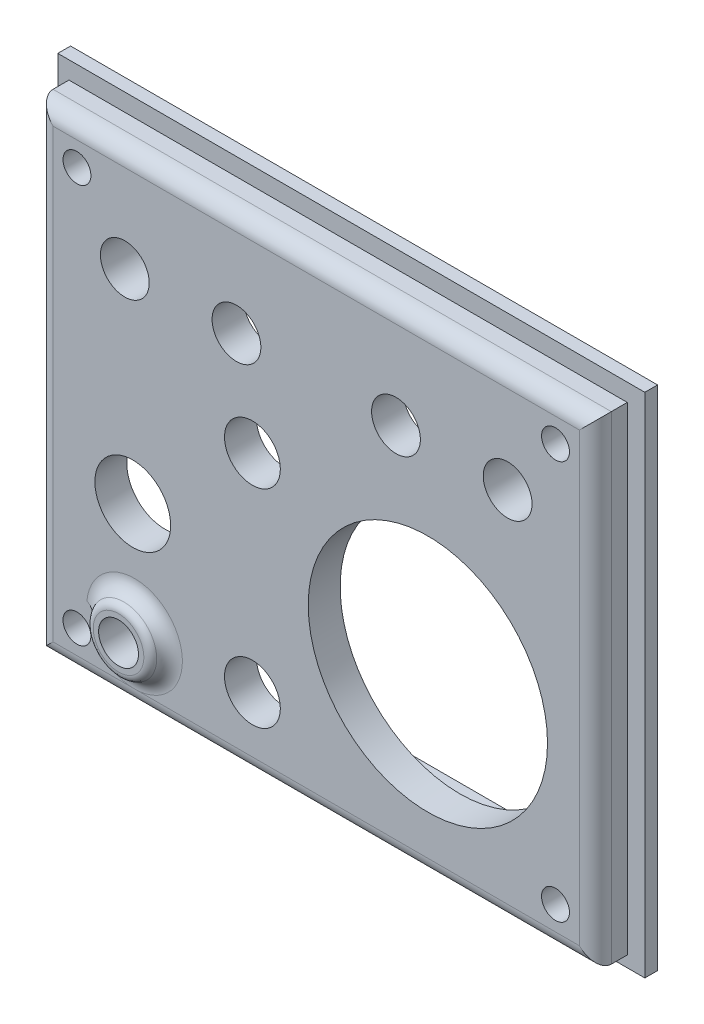
SolidWorks part; units mm, degrees
ref_plane "Спереди" through (0, 0, 0) normal (0, 0, 1) x (1, 0, 0)
ref_plane "Сверху" through (0, 0, 0) normal (0, 1, 0) x (1, 0, 0)
ref_plane "Справа" through (0, 0, 0) normal (1, 0, 0) x (0, 0, -1)
sketch "Sketch1" plane through (0, 0, 0) normal (0, 0, 1) x (1, 0, 0)
  line L1 (35, -30) -> (-35, -30)
  line L2 (35, -30) -> (35, 30)
  line L3 (35, 30) -> (-35, 30)
  line L4 (-35, -30) -> (-35, 30)
  line L5 (35, -30) -> (-35, 30) construction
  line L6 (35, 30) -> (-35, -30) construction
  point P0 (0, 0)
  dimension "D1" = 70
  dimension "D2" = 60
extrude "Boss-Extrude1" add sketch "Sketch1" along normal blind 4
sketch "Sketch2" plane through (0, 0, 0) normal (0, 0, -1) x (-1, 0, 0)
  line L0 (35, -30) -> (-35, -30) construction
  line L1 (-31.8, 26.8) -> (31.8, 26.8)
  line L2 (-31.8, 26.8) -> (-31.8, -26.8)
  line L3 (-31.8, -26.8) -> (31.8, -26.8)
  line L4 (31.8, 26.8) -> (31.8, -26.8)
  line L5 (-31.8, 26.8) -> (31.8, -26.8) construction
  line L6 (-31.8, -26.8) -> (31.8, 26.8) construction
  line L7 (-35, -30) -> (-35, 30) construction
  line L9 (28.8, -23.8) -> (-28.8, -23.8)
  line L10 (28.8, -23.8) -> (28.8, 23.8)
  line L11 (28.8, 23.8) -> (-28.8, 23.8)
  line L12 (-28.8, -23.8) -> (-28.8, 23.8)
  line L13 (28.8, -23.8) -> (-28.8, 23.8) construction
  line L14 (28.8, 23.8) -> (-28.8, -23.8) construction
  point P0 (0, 0)
  point P10 (0, 0)
  dimension "D1" = 3.2
  dimension "D2" = 3.2
  dimension "D3" = 3
  dimension "D4" = 3
extrude "Boss-Extrude2" add sketch "Sketch2" along normal blind 2
chamfer "Chamfer1" distance 0.5 angle 70 4 edges at (-31.8, 0, -2) (0, 26.8, -2) (31.8, 0, -2) (0, -26.8, -2) first distance on face at (0, 0, -2)
fillet "Fillet1" radius 2 4 edges at (0, 30, 4) (35, 0, 4) (0, -30, 4) (-35, 0, 4)
sketch "Sketch3" plane through (0, 0, 4) normal (0, 0, 1) x (1, 0, 0)
  line L0 (0, -41.7208) -> (0, 41.7208) construction
  line L1 (33, 17) -> (-33, 17) construction
  line L2 (-33, 28) -> (-33, -28) construction
  circle A1 centre (-24, 17) radius 3.0603
  circle A2 centre (10, 17) radius 3.0603
  circle A4 centre (-10, 17) radius 3.0603
  circle A5 centre (24, 17) radius 3.0603
  point P4 (0, 0)
  point P11 (0, 17)
  point P13 (-10, 17)
  dimension "D1" = 14
  dimension "D2" = 17
  dimension "D3" = 20
  dimension "D4" = 10
  dimension "D7" = 14
extrude "Cut-Extrude1" cut sketch "Sketch3" against normal through all
sketch "Sketch4" plane through (0, 0, 4) normal (0, 0, 1) x (1, 0, 0)
  line L0 (0, -40.1993) -> (0, 40.1993) construction
  line L1 (0, 0) -> (33, 0) construction
  line L2 (33, -28) -> (33, 28) construction
  line L3 (14, -8) -> (0, -8) construction
  circle A0 centre (14, -8) radius 15
  point P3 (0, 0)
  dimension "D1" = 30
  dimension "D2" = 8
  dimension "D3" = 14
extrude "Cut-Extrude2" cut sketch "Sketch4" against normal through all
sketch "Sketch5" plane through (0, 0, 4) normal (0, 0, 1) x (1, 0, 0)
  line L0 (-8, 28) -> (-8, -28) construction
  line L1 (33, 28) -> (-33, 28) construction
  line L2 (-33, -28) -> (33, -28) construction
  line L3 (14, -8) -> (-8, -8) construction
  line L4 (14, -8) -> (14, 28) construction
  circle A0 centre (-8, 5) radius 3.5
  circle A1 centre (-8, -21) radius 3.5
  dimension "D1" = 26
  dimension "D2" = 7
  dimension "D3" = 13
  dimension "D4" = 22
extrude "Cut-Extrude3" cut sketch "Sketch5" against normal through all
sketch "Sketch6" plane through (0, 0, 0) normal (0, 0, -1) x (-1, 0, 0)
  circle A0 centre (24, 17) radius 5
  circle A1 centre (-24, 17) radius 5
  circle A2 centre (-24, 17) radius 3.0603
  circle A3 centre (24, 17) radius 3.0603
  dimension "D1" = 10
extrude "Boss-Extrude3" add sketch "Sketch6" along normal blind 2
fillet "Fillet2" radius 1 3 edges at (28.8, 23.8, -1) (28.8, 18.4, -1) (28.8, 15.6, -1)
sketch "Sketch7" plane through (0, 0, -2) normal (0, 0, -1) x (-1, 0, 0)
  line L0 (15, 27.7408) -> (15, -32.2592)
  line L2 (15, -32.2592) -> (35, -32.2592)
  line L3 (35, -32.2592) -> (35, 27.7408)
  line L4 (35, 27.7408) -> (15, 27.7408)
  line L5 (35, 30) -> (35, -30) construction
  dimension "D1" = 20
  dimension "D2" = 60
extrude "Cut-Extrude4" cut sketch "Sketch7" against normal up to surface (2 mm away) up to face at (0, 0, 0)
sketch "Sketch8" plane through (0, 0, 0) normal (0, 0, -1) x (-1, 0, 0)
  line L0 (23, 30) -> (23, -30) construction
  line L1 (-35, 30) -> (35, 30) construction
  line L2 (35, -30) -> (-35, -30) construction
  line L3 (35, 30) -> (35, -30) construction
  line L4 (-14, -8) -> (23, -8) construction
  circle A0 centre (23, -8) radius 4.75
  dimension "D1" = 9.5
  dimension "D2" = 12
extrude "Cut-Extrude5" cut sketch "Sketch8" against normal through all
sketch "Sketch9" plane through (0, 0, 0) normal (0, 0, -1) x (-1, 0, 0)
  line L0 (35, 30) -> (35, -30) construction
  line L1 (-30, -25) -> (30, -25) construction
  line L2 (-30, -25) -> (-30, 25) construction
  line L3 (-30, 25) -> (30, 25) construction
  line L4 (30, -25) -> (30, 25) construction
  line L5 (-30, -25) -> (30, 25) construction
  line L6 (-30, 25) -> (30, -25) construction
  line L7 (35, -30) -> (-35, -30) construction
  circle A0 centre (30, 25) radius 1.75
  circle A1 centre (30, -25) radius 1.75
  circle A2 centre (-30, -25) radius 1.75
  circle A3 centre (-30, 25) radius 1.75
  point P0 (0, 0)
  dimension "D3" = 3.5
  dimension "D1" = 5
  dimension "D2" = 5
extrude "Cut-Extrude6" cut sketch "Sketch9" against normal through all both and the other way through all
sketch "Sketch10" plane through (0, 0, 0) normal (0, 0, -1) x (-1, 0, 0)
  line L0 (23, -8) -> (23, 1) construction
  circle A0 centre (23, 1) radius 2
  dimension "D2" = 4
  dimension "D1" = 9
extrude "Cut-Extrude7" cut sketch "Sketch10" against normal blind 2
sketch "Sketch11" plane through (0, 0, 0) normal (0, 0, -1) x (-1, 0, 0)
  circle A0 centre (24, 17) radius 5
  circle A1 centre (24, 17) radius 3.0603
  arc A2 (-27.1667, 13.1306) -> (-27.1667, 20.8694) centre (-24, 17) ccw construction
  circle A3 centre (-24, 17) radius 3.0603 construction
extrude "Boss-Extrude4" add sketch "Sketch11" along normal up to surface (2 mm away) up to face at (1.8381, -24.7536, -2)
sketch "Sketch12" plane through (0, 0, 0) normal (0, 0, -1) x (-1, 0, 0)
  circle A0 centre (-30, 25) radius 5
  circle A1 centre (-30, -25) radius 5
  dimension "D1" = 10
extrude "Cut-Extrude9" cut sketch "Sketch12" along normal through all
sketch "Sketch13" plane through (0, 0, 0) normal (0, 0, -1) x (-1, 0, 0)
  line L0 (35, -22) -> (-35, -22) construction
  line L1 (35, 30) -> (35, -30) construction
  line L2 (-35, -30) -> (-35, 30) construction
  line L3 (35, -30) -> (-35, -30) construction
  circle A0 centre (22.7832, -22) radius 2.5
  dimension "D1" = 5
  dimension "D2" = 8
extrude "Cut-Extrude10" cut sketch "Sketch13" against normal through all
sketch "Sketch14" plane through (0, 0, 0) normal (0, 0, -1) x (-1, 0, 0)
  line L1 (19.5332, -18.75) -> (26.0332, -18.75)
  line L2 (19.5332, -18.75) -> (19.5332, -25.25)
  line L3 (19.5332, -25.25) -> (26.0332, -25.25)
  line L4 (26.0332, -18.75) -> (26.0332, -25.25)
  line L5 (19.5332, -18.75) -> (26.0332, -25.25) construction
  line L6 (19.5332, -25.25) -> (26.0332, -18.75) construction
  line L7 (18.2832, -17.5) -> (27.2832, -17.5)
  line L8 (18.2832, -17.5) -> (18.2832, -26.5)
  line L9 (18.2832, -26.5) -> (27.2832, -26.5)
  line L10 (27.2832, -17.5) -> (27.2832, -26.5)
  line L11 (18.2832, -17.5) -> (27.2832, -26.5) construction
  line L12 (18.2832, -26.5) -> (27.2832, -17.5) construction
  point P0 (22.7832, -22)
  point P6 (22.7832, -22)
  dimension "D1" = 6.5
  dimension "D2" = 9
extrude "Boss-Extrude5" add sketch "Sketch14" along normal up to surface (2 mm away) up to face at (0.6932, -24.7503, -2)
sketch "Sketch17" plane through (0, 0, 4) normal (0, 0, 1) x (1, 0, 0)
  circle A0 centre (-22.7832, -22) radius 2.5
  circle A1 centre (-22.7832, -22) radius 4
  circle A2 centre (-22.7832, -22) radius 2.5 construction
  dimension "D1" = 8
extrude "Boss-Extrude7" add sketch "Sketch17" along normal blind 2
fillet "Fillet5" radius 2 1 edges at (-18.7832, -22, 4)
fillet "Fillet6" radius 1 1 edges at (-18.7832, -22, 6)
sketch "Sketch18" plane through (0, 0, 4) normal (0, 0, 1) x (1, 0, 0)
  circle A0 centre (-30, -25) radius 3.75
  dimension "D1" = 7.5
extrude "Cut-Extrude13" cut sketch "Sketch18" along normal through all
sketch "Sketch19" plane through (0, 0, 0) normal (0, 0, -1) x (-1, 0, 0)
  line L0 (-31.8, -20.3352) -> (-31.8, 20.3352) construction
  line L1 (32.8, 27.8) -> (-32.8, 27.8)
  line L2 (32.8, 27.8) -> (32.8, -27.8)
  line L3 (32.8, -27.8) -> (-32.8, -27.8)
  line L4 (-32.8, 27.8) -> (-32.8, -27.8)
  line L5 (32.8, 27.8) -> (-32.8, -27.8) construction
  line L6 (32.8, -27.8) -> (-32.8, 27.8) construction
  line L7 (-36.8, 31.8) -> (36.8, 31.8)
  line L8 (-36.8, 31.8) -> (-36.8, -31.8)
  line L9 (-36.8, -31.8) -> (36.8, -31.8)
  line L10 (36.8, 31.8) -> (36.8, -31.8)
  line L11 (-36.8, 31.8) -> (36.8, -31.8) construction
  line L12 (-36.8, -31.8) -> (36.8, 31.8) construction
  line L13 (-25.3352, -26.8) -> (15, -26.8) construction
  point P0 (0, 0)
  point P6 (0, 0)
  dimension "D1" = 1
  dimension "D2" = 4
  dimension "D3" = 4
  dimension "D4" = 1
extrude "Boss-Extrude8" add sketch "Sketch19" along normal up to surface (2 mm away) from offset 0.4 separate body up to face at (0.6932, -24.7503, -2)
sketch "Sketch21" plane through (0, 0, 0) normal (0, 0, -1) x (-1, 0, 0)
  circle A0 centre (8, -21) radius 9.0907
extrude "Cut-Extrude15" cut sketch "Sketch21" along normal through all
sketch "Sketch20" plane through (0, 0, -2) normal (0, 0, -1) x (-1, 0, 0)
  line L0 (32.8, 27.8) -> (-32.8, 27.8) construction
  line L1 (32.8, -27.8) -> (32.8, 27.8) construction
  line L2 (-32.8, -27.8) -> (32.8, -27.8) construction
  line L3 (-32.8, 27.8) -> (-32.8, -27.8) construction
  line L4 (-27.2562, 27.8) -> (-32.8, 27.8)
  line L5 (-32.8, 27.8) -> (-32.8, 22.2562)
  line L6 (-32.8, -22.2562) -> (-32.8, -27.8)
  line L7 (-32.8, -27.8) -> (-27.2562, -27.8)
  line L8 (25.8802, 27.8) -> (32.8, 27.8)
  line L9 (32.8, 27.8) -> (32.8, 20.5583)
  line L10 (27.8424, -27.8) -> (27.8424, -21.5441)
  line L11 (32.8, -21.5441) -> (32.8, -27.8)
  line L12 (32.8, -27.8) -> (27.8424, -27.8)
  line L13 (27.8424, -21.5441) -> (32.8, -21.5441)
  arc A0 (25.8802, 27.8) -> (32.8, 20.5583) centre (34.3418, 28.9585) ccw
  arc A2 (-27.2562, 27.8) -> (-32.8, 22.2562) centre (-30.5342, 25.5342) cw
  arc A3 (-32.8, -22.2562) -> (-27.2562, -27.8) centre (-30.5342, -25.5342) cw
extrude "support" add sketch "Sketch20" against normal up to surface (1.6 mm away) up to face at (0, 0, -0.4)
